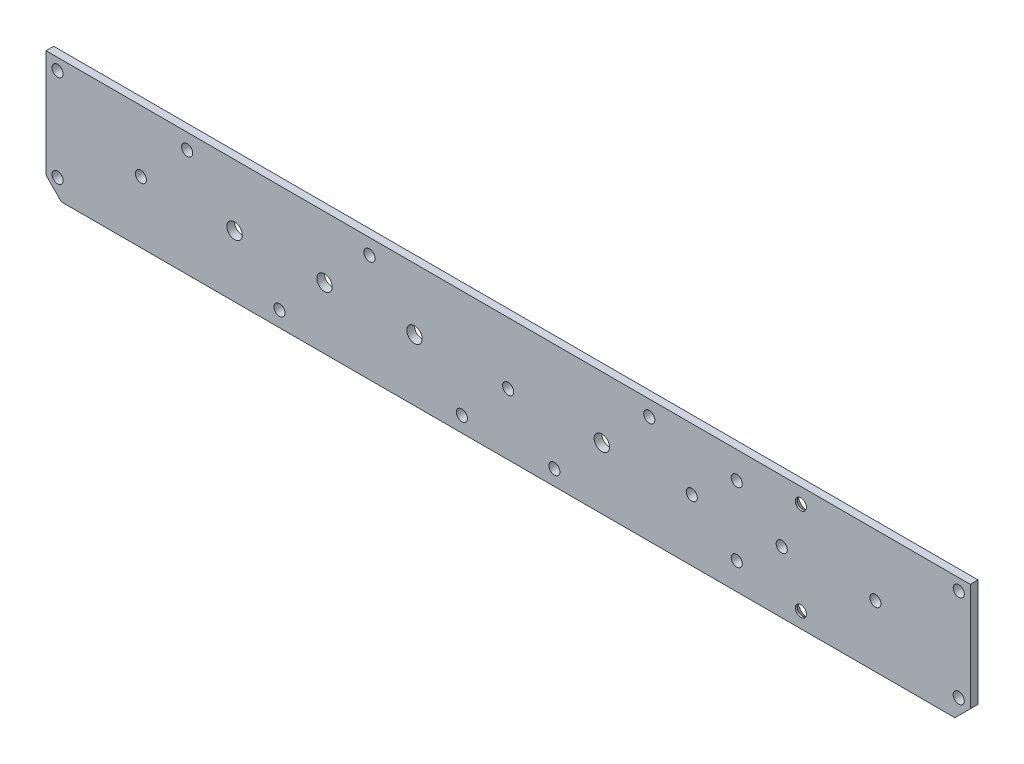
SolidWorks part; units mm, degrees
ref_plane "Front Plane" through (0, 0, 0) normal (0, 0, 1) x (1, 0, 0)
ref_plane "Top Plane" through (0, 0, 0) normal (0, 1, 0) x (1, 0, 0)
ref_plane "Right Plane" through (0, 0, 0) normal (1, 0, 0) x (0, 0, -1)
sketch "Sketch1" plane through (0, 0, 0) normal (0, 0, 1) x (1, 0, 0)
  line L1 (0, 0) -> (381, 0)
  line L2 (0, 0) -> (0, 50.8)
  line L3 (0, 50.8) -> (381, 50.8)
  line L4 (381, 0) -> (381, 50.8)
  dimension "D1" = 50.8
  dimension "D2" = 381
extrude "Boss-Extrude1" add sketch "Sketch1" along normal blind 3.175
sketch "Sketch2" plane through (0, 0, 3.175) normal (0, 0, 1) x (1, 0, 0)
  line L0 (77.724, 25.4) -> (114.808, 25.4) construction
  line L1 (190.5, 50.8) -> (190.5, 0) construction
  line L2 (381, 50.8) -> (0, 50.8) construction
  line L3 (0, 0) -> (381, 0) construction
  line L4 (266.192, 25.4) -> (303.276, 25.4) construction
  line L5 (0, 6.35) -> (0, 0)
  line L6 (0, 50.8) -> (0, 0) construction
  line L7 (0, 0) -> (6.35, 0)
  line L8 (6.35, 0) -> (0, 6.35)
  line L9 (381, 0) -> (374.65, 0)
  line L10 (374.65, 0) -> (381, 6.35)
  line L11 (381, 6.35) -> (381, 0)
  line L12 (381, 0) -> (381, 50.8) construction
  circle A0 centre (39.116, 25.4) radius 2.286
  circle A1 centre (190.5, 25.4) radius 2.286
  circle A2 centre (114.808, 25.4) radius 3.175
  circle A3 centre (77.724, 25.4) radius 3.175
  circle A4 centre (151.892, 25.4) radius 3.175
  circle A5 centre (229.108, 25.4) radius 3.175
  circle A6 centre (303.276, 25.4) radius 2.286
  circle A7 centre (266.192, 25.4) radius 2.286
  circle A8 centre (341.884, 25.4) radius 2.286
  circle A9 centre (58.166, 44.45) radius 2.286
  circle A10 centre (171.45, 6.35) radius 2.286
  circle A11 centre (209.55, 6.35) radius 2.286
  circle A13 centre (133.35, 44.45) radius 2.286
  circle A14 centre (248.666, 44.45) radius 2.286
  circle A15 centre (96.266, 6.35) radius 2.286
  circle A19 centre (4.7625, 46.0375) radius 2.286
  circle A20 centre (4.7625, 7.9375) radius 2.286
  circle A21 centre (376.2375, 7.9375) radius 2.286
  circle A22 centre (376.2375, 46.0375) radius 2.286
  circle A24 centre (311.15, 44.45) radius 2.286
  circle A25 centre (284.734, 11.1125) radius 2.286
  circle A26 centre (284.734, 39.6875) radius 2.286
  circle A27 centre (311.15, 6.35) radius 2.286
  point P17 (190.5, 25.4)
  point P38 (96.266, 25.4)
  point P49 (284.734, 25.4)
  point P66 (0, 0)
  dimension "D2" = 4.572
  dimension "D5" = 6.35
  dimension "D7" = 4.572
  dimension "D12" = 4.572
  dimension "D15" = 4.572
  dimension "D16" = 4.572
  dimension "D19" = 4.572
  dimension "D21" = 6.35
  dimension "D27" = 4.572
  dimension "D29" = 11.1125
  dimension "D8" = 4.572
  dimension "D10" = 4.572
  dimension "D13" = 6.35
  dimension "D3" = 38.608
  dimension "D6" = 14.2875
  dimension "D9" = 69.85
  dimension "D11" = 6.35
  dimension "D22" = 6.35
  dimension "D25" = 4.7625
  dimension "D26" = 4.7625
  dimension "D28" = 7.9375
extrude "Cut-Extrude1" cut sketch "Sketch2" against normal up to next (3.175 mm away)
chamfer "Chamfer1" distance 2.3813 angle 41 2 edges at (308.864, 44.45, 0) (308.864, 6.35, 0) first distance on face at (308.864, 44.45, 0) first distance on face at (308.864, 6.35, 0)
